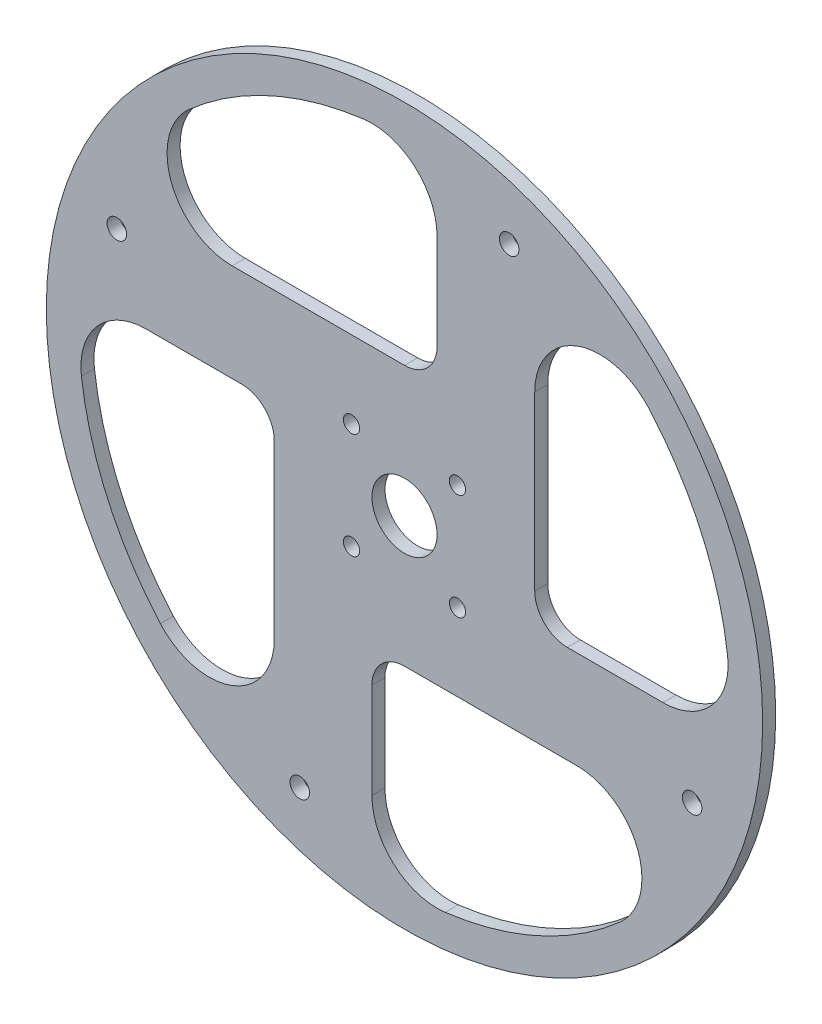
SolidWorks part; units mm, degrees
material "AISI 316 不锈钢板 (SS)"
ref_plane "前视基准面" through (0, 0, 0) normal (0, 0, 1) x (1, 0, 0)
ref_plane "上视基准面" through (0, 0, 0) normal (0, 1, 0) x (1, 0, 0)
ref_plane "右视基准面" through (0, 0, 0) normal (1, 0, 0) x (0, 0, -1)
other "Configuration Table"
sketch "草图1" plane through (0, 0, 0) normal (0, 0, 1) x (1, 0, 0)
  line L0 (0, 0) -> (0, 16.9097) construction
  line L5 (0, 0) -> (-8.1317, 8.1317) construction
  line L10 (0, 20) -> (-26.4575, 20)
  line L11 (-19.3649, 5) -> (-49.7494, 5) construction
  line L18 (7.3863, 0) -> (-76.4712, 0) construction
  line L19 (-25, 5) -> (-39.6863, 5)
  line L20 (0, 0) -> (-44.1656, 16.0749) construction
  line L24 (20, 0) -> (20, 26.4575)
  line L25 (5, 25) -> (5, 39.6863)
  line L26 (0, 0) -> (8.1317, 8.1317) construction
  line L28 (0, 0) -> (16.0749, 44.1656) construction
  line L29 (0, -20) -> (26.4575, -20)
  line L30 (25, -5) -> (39.6863, -5)
  line L31 (0, 0) -> (8.1317, -8.1317) construction
  line L33 (0, 0) -> (44.1656, -16.0749) construction
  line L34 (-20, 0) -> (-20, -26.4575)
  line L35 (-5, -25) -> (-5, -39.6863)
  line L36 (0, 0) -> (-8.1317, -8.1317) construction
  line L38 (0, 0) -> (-16.0749, -44.1656) construction
  line L39 (5, 19.3649) -> (5, 49.7494) construction
  line L40 (-5, -19.3649) -> (-5, -49.7494) construction
  line L41 (19.3649, -5) -> (49.7494, -5) construction
  circle A0 centre (0, 0) radius 55
  circle A2 centre (0, 0) radius 11.5 construction
  circle A3 centre (-8.1317, 8.1317) radius 1.25
  circle A4 centre (8.1317, 8.1317) radius 1.25
  circle A5 centre (8.1317, -8.1317) radius 1.25
  circle A6 centre (-8.1317, -8.1317) radius 1.25
  circle A7 centre (0, 0) radius 5
  arc A11 (-19.3649, 5) -> (-20, 0) centre (0, 0) ccw construction
  arc A13 (-49.6078, -6.25) -> (-33.0719, 37.5) centre (0, 0) ccw construction
  arc A18 (-20, 0) -> (-25, 5) centre (-25, 0) ccw
  arc A19 (-39.6863, 5) -> (-49.6078, -6.25) centre (-39.6863, -5) ccw
  arc A20 (-26.4575, 20) -> (-33.0719, 37.5) centre (-26.4575, 30) cw
  circle A21 centre (0, 0) radius 50 construction
  circle A22 centre (-44.1656, 16.0749) radius 1.5
  arc A23 (0, 20) -> (5, 25) centre (0, 25) ccw
  arc A24 (5, 39.6863) -> (-6.25, 49.6078) centre (-5, 39.6863) ccw
  arc A25 (20, 26.4575) -> (37.5, 33.0719) centre (30, 26.4575) cw
  circle A26 centre (16.0749, 44.1656) radius 1.5
  arc A27 (-33.0719, 37.5) -> (-6.25, 49.6078) centre (0, 0) cw
  arc A28 (20, 0) -> (25, -5) centre (25, 0) ccw
  arc A29 (39.6863, -5) -> (49.6078, 6.25) centre (39.6863, 5) ccw
  arc A30 (26.4575, -20) -> (33.0719, -37.5) centre (26.4575, -30) cw
  circle A31 centre (44.1656, -16.0749) radius 1.5
  arc A32 (37.5, 33.0719) -> (50, 0) centre (0, 0) cw
  arc A33 (0, -20) -> (-5, -25) centre (0, -25) ccw
  arc A34 (-5, -39.6863) -> (6.25, -49.6078) centre (5, -39.6863) ccw
  arc A35 (-20, -26.4575) -> (-37.5, -33.0719) centre (-30, -26.4575) cw
  circle A36 centre (-16.0749, -44.1656) radius 1.5
  arc A37 (33.0719, -37.5) -> (0, -50) centre (0, 0) cw
  arc A38 (-5, -19.3649) -> (0, -20) centre (0, 0) ccw construction
  arc A39 (5, 19.3649) -> (0, 20) centre (0, 0) ccw construction
  arc A40 (19.3649, -5) -> (20, 0) centre (0, 0) ccw construction
  arc A41 (-37.5, -33.0719) -> (-49.6078, -6.25) centre (0, 0) cw
  point P18 (0, 0)
  point P33 (0, 0)
  point P37 (0, 0)
  point P57 (0, 0)
  point P66 (0, 0)
  point P74 (0, 0)
  point P83 (0, 0)
  point P91 (0, 0)
  point P97 (0, 0)
  dimension "D1" = 110
  dimension "D2" = 5
  dimension "D3" = 23
  dimension "D4" = 2.5
  dimension "D7" = 10
  dimension "D8" = 4
  dimension "D11" = 10
  dimension "D12" = 10
  dimension "D13" = 3
  dimension "D15" = 20
  dimension "D5" = 45
  dimension "D9" = 15
  dimension "D10" = 20
  dimension "D14" = 47
  dimension "D6" = 4
extrude "凸台-拉伸1" add sketch "草图1" along normal blind 2 contours A0 A36 A31 A26 A22 A7 A6 A5 A4 A3 A20 A27 A24 L25 A23 L10 A25 A32 A29 L30 A28 L24 A30 A37 A34 L35 A33 L29 A35 A41 A19 L19 A18 L34 region at (-53.4444, 0, 0)
